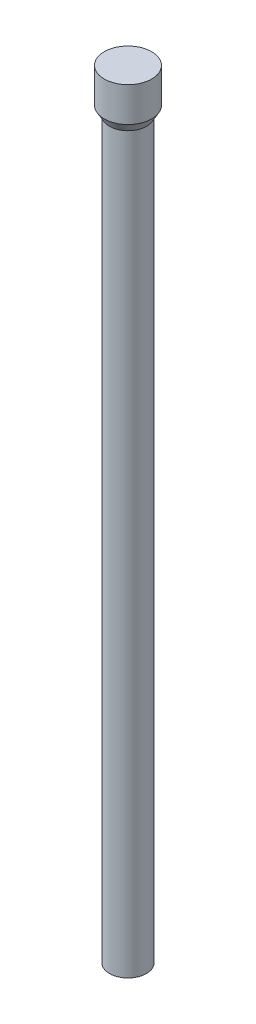
SolidWorks part; units mm, degrees
ref_plane "前视基准面" through (0, 0, 0) normal (0, 0, 1) x (1, 0, 0)
ref_plane "上视基准面" through (0, 0, 0) normal (0, 1, 0) x (1, 0, 0)
ref_plane "右视基准面" through (0, 0, 0) normal (1, 0, 0) x (0, 0, -1)
other "Configuration Table"
sketch "草图1" plane through (0, 0, 0) normal (0, 1, 0) x (1, 0, 0)
  circle A0 centre (0, 0) radius 2.5
  circle A1 centre (0, 0) radius 2
extrude "凸台-拉伸1" add sketch "草图1" along normal blind 2 contours A0
sketch "草图2" plane through (0, 0, 0) normal (0, -1, 0) x (1, 0, 0)
  circle A0 centre (0, 0) radius 1.95
extrude "凸台-拉伸2" add sketch "草图2" along normal blind 80
chamfer "倒角1" distance 1.5 angle 60 1 edges at (0, 0, -1.95) first distance on face at (0, 0, -1.95)
